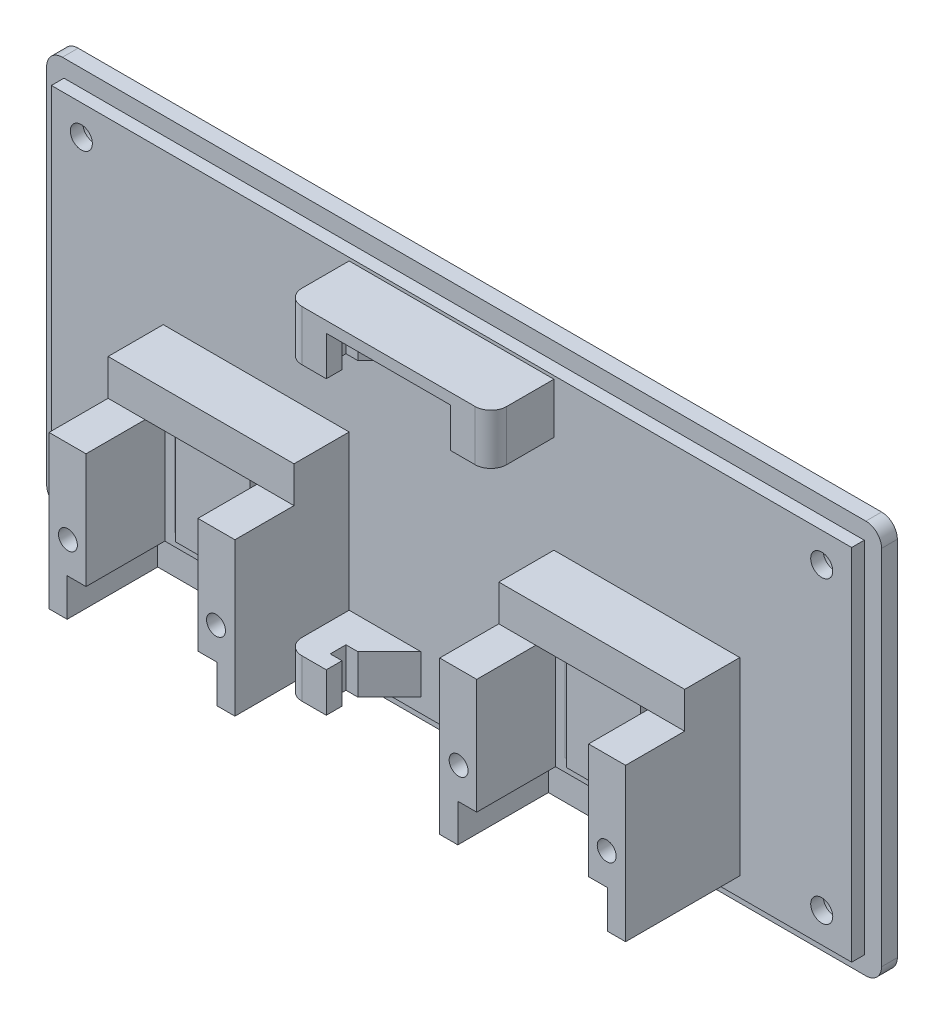
SolidWorks part; units mm, degrees
material "ABS"
ref_plane "Спереди" through (0, 0, 0) normal (0, 0, 1) x (1, 0, 0)
ref_plane "Сверху" through (0, 0, 0) normal (0, 1, 0) x (1, 0, 0)
ref_plane "Справа" through (0, 0, 0) normal (1, 0, 0) x (0, 0, -1)
sketch "Эскиз1" plane through (0, 0, 0) normal (0, 0, 1) x (1, 0, 0)
  line L1 (-53, -25) -> (53, -25)
  line L2 (-53, -25) -> (-53, 25)
  line L3 (-53, 25) -> (53, 25)
  line L4 (53, -25) -> (53, 25)
  line L5 (-53, -25) -> (53, 25) construction
  line L6 (-53, 25) -> (53, -25) construction
  point P0 (0, 0)
  dimension "D1" = 106
  dimension "D2" = 50
extrude "Body" add sketch "Эскиз1" along normal blind 2
sketch "Эскиз2" plane through (0, 0, 2) normal (0, 0, 1) x (1, 0, 0)
  line L0 (-53, 25) -> (-53, -25) construction
  line L1 (-50.8, -22.8) -> (50.8, -22.8)
  line L2 (-50.8, -22.8) -> (-50.8, 22.8)
  line L3 (-50.8, 22.8) -> (50.8, 22.8)
  line L4 (50.8, -22.8) -> (50.8, 22.8)
  line L5 (-50.8, -22.8) -> (50.8, 22.8) construction
  line L6 (-50.8, 22.8) -> (50.8, -22.8) construction
  line L7 (53, 25) -> (-53, 25) construction
  point P0 (0, 0)
  dimension "D1" = 2.2
  dimension "D2" = 2.2
extrude "InternalBody" add sketch "Эскиз2" along normal blind 1.6
sketch "Эскиз3" plane through (0, 0, 0) normal (0, 0, -1) x (-1, 0, 0)
  line L0 (53, -25) -> (-53, -25) construction
  line L1 (51, -23) -> (43, -23) construction
  line L2 (51, -23) -> (51, -15) construction
  line L3 (51, -15) -> (43, -15) construction
  line L4 (43, -23) -> (43, -15) construction
  line L5 (51, -23) -> (43, -15) construction
  line L6 (51, -15) -> (43, -23) construction
  line L7 (53, 25) -> (53, -25) construction
  circle A0 centre (47, -19) radius 1.4
  circle A1 centre (47, -19) radius 2.5
  point P0 (47, -19)
  dimension "D4" = 2.8
  dimension "D5" = 5
  dimension "D1" = 2
  dimension "D2" = 2
  dimension "D3" = 8
extrude "HoleScrew" cut sketch "Эскиз3" against normal through all contours A0 region at (-47, -19, 0)
extrude "TopScrewPlace" cut sketch "Эскиз3<3>" against normal blind 2 contours A1 A0 region at (-44.5707, -19, 0)
sketch "Эскиз3<3>" plane through (0, 0, 0) normal (0, 0, -1) x (-1, 0, 0) same geometry as "Эскиз3"
mirror "ScrewMrror1" about plane through (0, 0, 0) normal (0, 1, 0) of "TopScrewPlace", "HoleScrew"
mirror "ScrewMirror2" about plane through (0, 0, 0) normal (1, 0, 0) of "ScrewMrror1", "TopScrewPlace"
fillet "Corners" radius 2 4 edges at (-53, -25, 1) (53, -25, 1) (53, 25, 1) (-53, 25, 1)
sketch "Эскиз4" plane through (0, 0, 3.6) normal (0, 0, 1) x (1, 0, 0)
  line L1 (13, 22.4) -> (-13, 22.4)
  line L2 (13, 22.4) -> (13, 21)
  line L3 (13, 21) -> (-13, 21)
  line L4 (-13, 22.4) -> (-13, 21)
  line L5 (13, 22.4) -> (-13, 21) construction
  line L6 (13, 21) -> (-13, 22.4) construction
  line L7 (50.8, 22.8) -> (-50.8, 22.8) construction
  point P0 (0, 21.7)
  dimension "D1" = 0.4
  dimension "D2" = 1.4
  dimension "D3" = 26
extrude "ArduinoNanoStops" add sketch "Эскиз4" along normal blind 8
sketch "Эскиз5" plane through (0, 21, 0) normal (0, -1, 0) x (1, 0, 0)
  line L0 (-7.9, 11.6) -> (-7.9, 9.6)
  line L1 (-13, 11.6) -> (13, 11.6) construction
  line L2 (-7.9, 9.6) -> (-9.4, 9.6)
  line L3 (-9.4, 9.6) -> (-9.4, 7.6)
  line L4 (-9.4, 7.6) -> (-7.9, 7.6)
  line L5 (-7.9, 7.6) -> (-7.9, 3.6)
  line L6 (-13, 3.6) -> (13, 3.6) construction
  line L7 (-7.9, 3.6) -> (-13, 3.6)
  line L8 (-13, 3.6) -> (-13, 11.6)
  line L9 (-13, 11.6) -> (-7.9, 11.6)
  line L10 (0, 0) -> (0, 19.1007) construction
  line L11 (7.9, 11.6) -> (7.9, 9.6)
  line L12 (7.9, 9.6) -> (9.4, 9.6)
  line L13 (9.4, 9.6) -> (9.4, 7.6)
  line L14 (9.4, 7.6) -> (7.9, 7.6)
  line L15 (7.9, 7.6) -> (7.9, 3.6)
  line L16 (7.9, 3.6) -> (13, 3.6)
  line L17 (13, 3.6) -> (13, 11.6)
  line L18 (13, 11.6) -> (7.9, 11.6)
  dimension "D1" = 15.8
  dimension "D2" = 18.8
  dimension "D3" = 2
  dimension "D4" = 2
extrude "ArduinoNanoHolder1" add sketch "Эскиз5" along normal blind 5
pattern_linear "ArduinoNanoHolder2" count 2 spacing 37 along (0, -1, 0) of "ArduinoNanoHolder1"
chamfer "An1" distance 4 angle 45 4 edges at (7.9, 18.5, 3.6) (7.9, -18.5, 3.6) (-7.9, -18.5, 3.6) (-7.9, 18.5, 3.6)
fillet "An2" radius 2 4 edges at (13, 19.2, 11.6) (13, -18.5, 11.6) (-13, -18.5, 11.6) (-13, 19.2, 11.6)
sketch "Эскиз6" plane through (0, 0, 3.6) normal (0, 0, 1) x (1, 0, 0)
  line L0 (-50.8, -22.8) -> (50.8, -22.8) construction
  line L1 (-36.6, 3.6) -> (-13, 3.6)
  line L2 (-36.6, 3.6) -> (-36.6, -20.4)
  line L3 (-36.6, -20.4) -> (-13, -20.4)
  line L4 (-13, 3.6) -> (-13, -20.4)
  line L5 (-36.6, 3.6) -> (-13, -20.4) construction
  line L6 (-36.6, -20.4) -> (-13, 3.6) construction
  line L7 (-13, -21) -> (-13, -16) construction
  point P0 (-24.8, -8.4)
  dimension "D1" = 2.4
  dimension "D2" = 24.8
  dimension "D3" = 24
extrude "NES1" add sketch "Эскиз6" along normal blind 3
sketch "Эскиз7" plane through (0, 0, 6.6) normal (0, 0, 1) x (1, 0, 0)
  line L0 (-13, -16) -> (-13, 3.6) construction
  line L1 (-36.6, 3.6) -> (-13, 3.6)
  line L2 (-36.6, 3.6) -> (-36.6, -1)
  line L3 (-36.6, -1) -> (-13, -1)
  line L4 (-13, 3.6) -> (-13, -1)
  dimension "D1" = 4.6
extrude "NES2" add sketch "Эскиз7" along normal blind 4
sketch "Эскиз8" plane through (0, 0, 6.6) normal (0, 0, 1) x (1, 0, 0)
  line L0 (-13, -16) -> (-13, -1) construction
  line L1 (-36.6, -1) -> (-13, -1)
  line L2 (-36.6, -1) -> (-36.6, -15.6)
  line L3 (-36.6, -15.6) -> (-13, -15.6)
  line L4 (-13, -1) -> (-13, -15.6)
  dimension "D1" = 14.6
extrude "NES3" add sketch "Эскиз8" along normal blind 1.5
sketch "Эскиз9" plane through (0, -1, 0) normal (0, -1, 0) x (1, 0, 0)
  line L0 (-13, 8.1) -> (-36.6, 8.1) construction
  line L1 (-24.8, 8.1) -> (-24.8, 16.1199) construction
  line L2 (-29.5168, 9.1) -> (-20.0832, 9.1)
  line L3 (-30.7, 8.1) -> (-18.9, 8.1)
  arc A0 (-30.7, 8.1) -> (-29.5168, 9.1) centre (-30.7, 9.3) ccw
  arc A1 (-20.0832, 9.1) -> (-18.9, 8.1) centre (-18.9, 9.3) ccw
  point P6 (-24.8, 8.1)
  dimension "D1" = 1.2
  dimension "D2" = 11.8
  dimension "D3" = 1
extrude "NES4" add sketch "Эскиз9" along normal blind 13
sketch "Эскиз10" plane through (0, 0, 8.1) normal (0, 0, 1) x (1, 0, 0)
  line L0 (-36.6, -15.6) -> (-13, -15.6) construction
  line L1 (-36.6, -1) -> (-31.9, -1)
  line L2 (-36.6, -1) -> (-36.6, -15.6)
  line L3 (-36.6, -15.6) -> (-31.9, -15.6)
  line L4 (-31.9, -1) -> (-31.9, -15.6)
  line L5 (-13, -1) -> (-17.7, -1)
  line L6 (-13, -1) -> (-13, -15.6)
  line L7 (-13, -15.6) -> (-17.7, -15.6)
  line L8 (-17.7, -1) -> (-17.7, -15.6)
  dimension "D1" = 4.7
extrude "NES5" add sketch "Эскиз10" along normal blind 10
sketch "Эскиз11" plane through (0, 0, 6.6) normal (0, 0, 1) x (1, 0, 0)
  line L0 (-36.6, -20.4) -> (-13, -20.4) construction
  line L1 (-36.6, -15.6) -> (-34.3, -15.6)
  line L2 (-36.6, -15.6) -> (-36.6, -20.4)
  line L3 (-36.6, -20.4) -> (-34.3, -20.4)
  line L4 (-34.3, -15.6) -> (-34.3, -20.4)
  line L6 (-13, -15.6) -> (-15.3, -15.6)
  line L7 (-13, -15.6) -> (-13, -20.4)
  line L8 (-13, -20.4) -> (-15.3, -20.4)
  line L9 (-15.3, -15.6) -> (-15.3, -20.4)
  dimension "D1" = 2.3
extrude "NES6" add sketch "Эскиз11" along normal up to surface (11.5 mm away) up to face at (-34.25, -8.3, 18.1)
sketch "Эскиз12" plane through (0, 0, 18.1) normal (0, 0, 1) x (1, 0, 0)
  line L1 (-24.8, -14.1106) -> (-24.8, -5.8091) construction
  line L2 (-20.0832, -1) -> (-29.5168, -1) construction
  line L3 (-34.3, -15.6) -> (-31.9, -15.6) construction
  circle A0 centre (-34.2, -11.6) radius 1.2
  circle A1 centre (-15.4, -11.6) radius 1.2
  point P6 (-24.8, -1)
  dimension "D2" = 2.4
  dimension "D1" = 4
  dimension "D3" = 18.8
extrude "NESFix" cut sketch "Эскиз12" against normal blind 6
mirror "SecondNES" about plane through (0, 0, 0) normal (1, 0, 0) of "NES2", "NES3", "NES4", "NES5", "NES6", "NESFix", "NES1"
equation "\"D3@Эскиз4\"=18+4*2"
equation "\"D1@Эскиз5\"=18+0.4*2-1.5*2"
